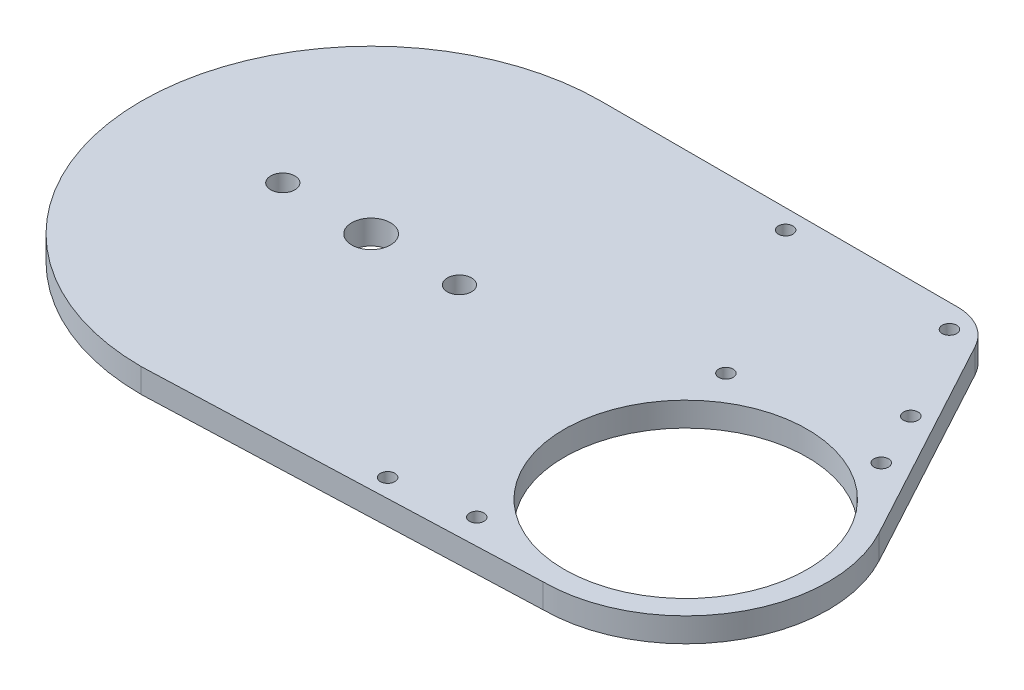
SolidWorks part; units mm, degrees
ref_plane "前视基准面" through (0, 0, 0) normal (0, 0, 1) x (1, 0, 0)
ref_plane "上视基准面" through (0, 0, 0) normal (0, 1, 0) x (1, 0, 0)
ref_plane "右视基准面" through (0, 0, 0) normal (1, 0, 0) x (0, 0, -1)
sketch "Sketch1" plane through (0, 0, 0) normal (0, 1, 0) x (1, 0, 0)
  line L0 (0, 0) -> (0, -15) construction
  line L1 (0, -15) -> (80, -15) construction
  line L2 (0, -47.5) -> (0, -44.5) construction
  line L3 (0, -44.5) -> (94.3585, -44.5) construction
  line L4 (0, -47.5) -> (80, -44.5)
  line L5 (0, 47.5) -> (73.764, 47.5)
  line L6 (82.559, 42.259) -> (105.9453, -0.9611)
  line L7 (73.764, 47.5) -> (82.559, 42.259) construction
  line L8 (78.8831, 46.0904) -> (76.8355, 42.6542) construction
  arc A0 (0, 47.5) -> (0, -47.5) centre (0, 0) ccw
  circle A1 centre (80, -15) radius 25.1
  arc A2 (80, -44.5) -> (105.9453, -0.9611) centre (80, -15) ccw
  circle A3 centre (75.0001, 47.5) radius 7.5 construction
  arc A4 (82.559, 42.259) -> (73.764, 47.5) centre (73.764, 37.5) ccw
  circle A5 centre (0, 0) radius 4
  circle A7 centre (93.688, 11.711) radius 1.5
  circle A8 centre (61.5917, 11.711) radius 1.5
  circle A9 centre (61.5917, -39.7686) radius 1.5
  circle A10 centre (0, 0) radius 18.25 construction
  circle A11 centre (18.25, 0) radius 2.5
  circle A12 centre (-18.25, 0) radius 2.5
  circle A13 centre (76.8355, 42.6542) radius 1.5
  circle A14 centre (42.1373, 43.5) radius 1.5
  circle A15 centre (88.3547, 23.1429) radius 1.5
  circle A16 centre (45.2934, -41.8851) radius 1.5
  dimension "D1" = 95
  dimension "D4" = 50.2
  dimension "D6" = 15
  dimension "D7" = 10
  dimension "D8" = 8
  dimension "D9" = 3
  dimension "D10" = 3
  dimension "D11" = 3
  dimension "D12" = 3
  dimension "D13" = 36.5
  dimension "D14" = 5
  dimension "D15" = 5
  dimension "D17" = 3
  dimension "D18" = 3
  dimension "D19" = 3
  dimension "D2" = 15
  dimension "D3" = 80
  dimension "D5" = 3
  dimension "D16" = 4
extrude "Boss-Extrude1" add sketch "Sketch1" along normal blind 5
